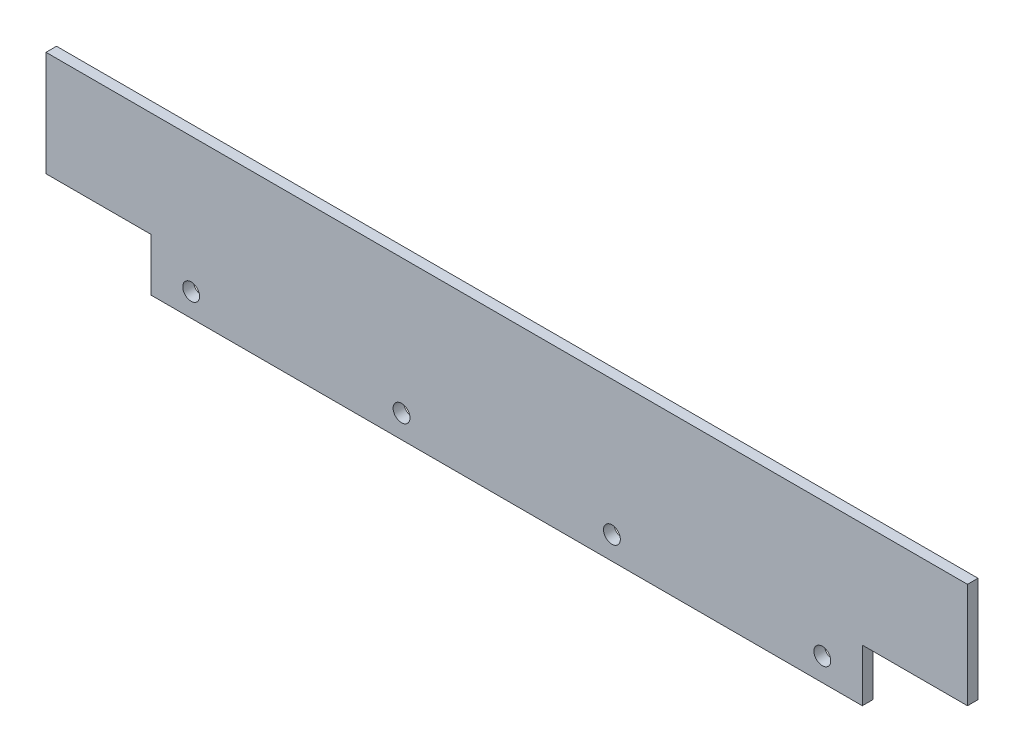
SolidWorks part; units mm, degrees
ref_plane "Alzado" through (0, 0, 0) normal (0, 0, 1) x (1, 0, 0)
ref_plane "Planta" through (0, 0, 0) normal (0, 1, 0) x (1, 0, 0)
ref_plane "Vista lateral" through (0, 0, 0) normal (1, 0, 0) x (0, 0, -1)
sketch "Croquis1" plane through (0, 0, 0) normal (0, 0, 1) x (1, 0, 0)
  line L0 (0, 0) -> (-338, 0)
  line L1 (-338, 0) -> (-338, 25)
  line L2 (-338, 25) -> (-388, 25)
  line L3 (-388, 25) -> (-388, 75)
  line L4 (-388, 75) -> (50, 75)
  line L5 (50, 75) -> (50, 25)
  line L6 (50, 25) -> (0, 25)
  line L7 (0, 25) -> (0, 0)
  line L8 (415.9078, 25) -> (-728.0032, 25) construction
  line L9 (44.691, 11) -> (-362.5608, 11) construction
  line L11 (-169, 75) -> (-169, -50.4144) construction
  circle A0 centre (-319, 11) radius 4
  circle A1 centre (-219, 11) radius 4
  circle A2 centre (-119, 11) radius 4
  circle A3 centre (-19, 11) radius 4
  dimension "D12" = 8
  dimension "D1" = 338
  dimension "D2" = 25
  dimension "D3" = 50
  dimension "D4" = 50
  dimension "D5" = 50
  dimension "D6" = 11
  dimension "D9" = 100
  dimension "D10" = 100
  dimension "D11" = 100
  dimension "D18" = 50
extrude "Saliente-Extruir1" add sketch "Croquis1" along normal blind 5
